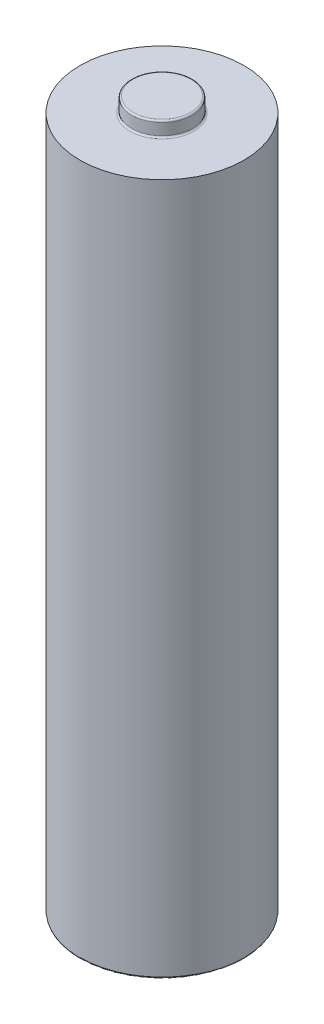
SolidWorks part; units mm, degrees
ref_plane "Front Plane" through (0, 0, 0) normal (0, 0, 1) x (1, 0, 0)
ref_plane "Top Plane" through (0, 0, 0) normal (0, 1, 0) x (1, 0, 0)
ref_plane "Right Plane" through (0, 0, 0) normal (1, 0, 0) x (0, 0, -1)
sketch "Sketch1" plane through (0, 0, 0) normal (0, 0, 1) x (1, 0, 0)
  line L0 (0, 0) -> (-2.7, 0)
  line L1 (-2.7, 0) -> (-2.7, 0.9)
  line L2 (-2.7, 0.9) -> (-5, 0.9)
  line L3 (-5, 0.9) -> (-5, 43.1)
  line L4 (-5, 43.1) -> (-1.85, 43.1)
  line L5 (-1.85, 43.1) -> (-1.85, 44)
  line L6 (-1.85, 44) -> (0, 44)
  line L7 (0, 44) -> (0, 0)
  dimension "D1" = 44
  dimension "D2" = 5
  dimension "D3" = 42.2
  dimension "D4" = 2.7
  dimension "D5" = 1.85
  dimension "D6" = 0.9
revolve "Revolve1" add sketch "Sketch1" angle 360 about L7
fillet "Fillet1" radius 0.1 5 edges at (-1.85, 43.1, 0) (-2.7, 0, 0) (-5, 0.9, 0) (-2.7, 0.9, 0) (-1.85, 44, 0)
ref_plane "Plane1" through (-5, 0, 0) normal (-1, 0, 0) x (0, 0, 1)
sketch "Sketch2" plane through (-5, 0, 0) normal (-1, 0, 0) x (0, 0, 1)
  line L0 (-1.9938, 41.1907) -> (-1.9938, 4.4047) construction
  text T0 "+   1.5V  AAA   - "
wrap "Wrap1" sketch "Sketch2" wrap type scribe source sketch "Sketch2" face at (5, 1, 0)
